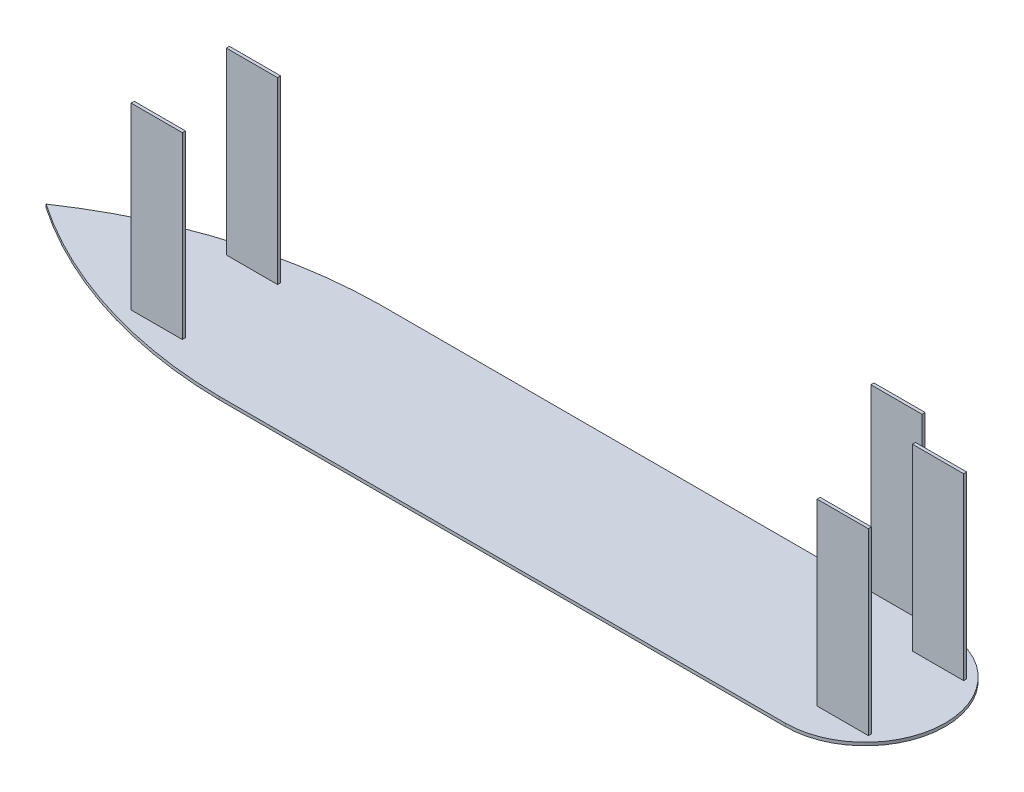
SolidWorks part; units mm, degrees
ref_plane "Front Plane" through (0, 0, 0) normal (0, 0, 1) x (1, 0, 0)
ref_plane "Top Plane" through (0, 0, 0) normal (0, 1, 0) x (1, 0, 0)
ref_plane "Right Plane" through (0, 0, 0) normal (1, 0, 0) x (0, 0, -1)
sketch "Sketch1" plane through (0, 0, 0) normal (0, 1, 0) x (1, 0, 0)
  line L0 (800, 78) -> (0, 78) construction
  line L1 (247.0699, 0) -> (800, 0)
  line L2 (0, 0) -> (0, 156) construction
  line L3 (247.0699, 156) -> (800, 156)
  arc A0 (800, 156) -> (800, 0) centre (800, 78) cw
  arc A1 (247.0699, 156) -> (0, 78) centre (253.6132, -295.0311) ccw
  arc A2 (247.0699, 0) -> (0, 78) centre (253.6132, 451.0311) cw
  point P6 (0, 0)
  point P12 (0, 0)
  point P13 (0, 0)
  dimension "D1" = 800
  dimension "D2" = 156
  dimension "D3" = 247.0699
extrude "Boss-Extrude1" add sketch "Sketch1" along normal blind 3
sketch "Sketch2" plane through (0, 3, 0) normal (0, 1, 0) x (1, 0, 0)
  line L0 (800, 156) -> (247.0699, 156) construction
  line L1 (801.0589, 126) -> (851.0589, 126)
  line L2 (801.0589, 126) -> (801.0589, 123)
  line L3 (801.0589, 123) -> (851.0589, 123)
  line L4 (851.0589, 126) -> (851.0589, 123)
  line L17 (730.4497, 156) -> (780.4497, 156)
  line L18 (730.4497, 156) -> (730.4497, 153)
  line L19 (730.4497, 153) -> (780.4497, 153)
  line L20 (780.4497, 156) -> (780.4497, 153)
  line L21 (247.0699, 0) -> (800, 0) construction
  line L22 (801.0589, 33) -> (851.0589, 33)
  line L23 (801.0589, 33) -> (801.0589, 30)
  line L24 (801.0589, 30) -> (851.0589, 30)
  line L25 (851.0589, 33) -> (851.0589, 30)
  line L27 (131.1174, 126) -> (181.1174, 126)
  line L28 (131.1174, 126) -> (131.1174, 123)
  line L29 (131.1174, 123) -> (181.1174, 123)
  line L30 (181.1174, 126) -> (181.1174, 123)
  line L31 (131.1174, 33) -> (181.1174, 33)
  line L32 (131.1174, 33) -> (131.1174, 30)
  line L33 (131.1174, 30) -> (181.1174, 30)
  line L34 (181.1174, 33) -> (181.1174, 30)
  point P25 (200.8911, 53.9821)
  dimension "D1" = 3
  dimension "D2" = 3
  dimension "D3" = 3
  dimension "D4" = 50
  dimension "D5" = 50
  dimension "D6" = 50
  dimension "D7" = 30
  dimension "D8" = 30
  dimension "D9" = 50
  dimension "D10" = 3
  dimension "D11" = 50
  dimension "D12" = 3
  dimension "D13" = 30
  dimension "D14" = 30
extrude "Boss-Extrude2" add sketch "Sketch2" along normal up to surface (175 mm away) contours L23 L24 L25 L22 | L2 L3 L4 L1 | L19 L20 L17 L18 up to face at (432.1397, 3, -78)
extrude "Boss-Extrude3" add sketch "Sketch2<4>" along normal up to surface (175 mm away) contours L31 L34 L33 L32 | L29 L30 L27 L28 up to face at (826.0589, 3, -124.5)
sketch "Sketch2<4>" plane through (0, 3, 0) normal (0, 1, 0) x (1, 0, 0) same geometry as "Sketch2"
